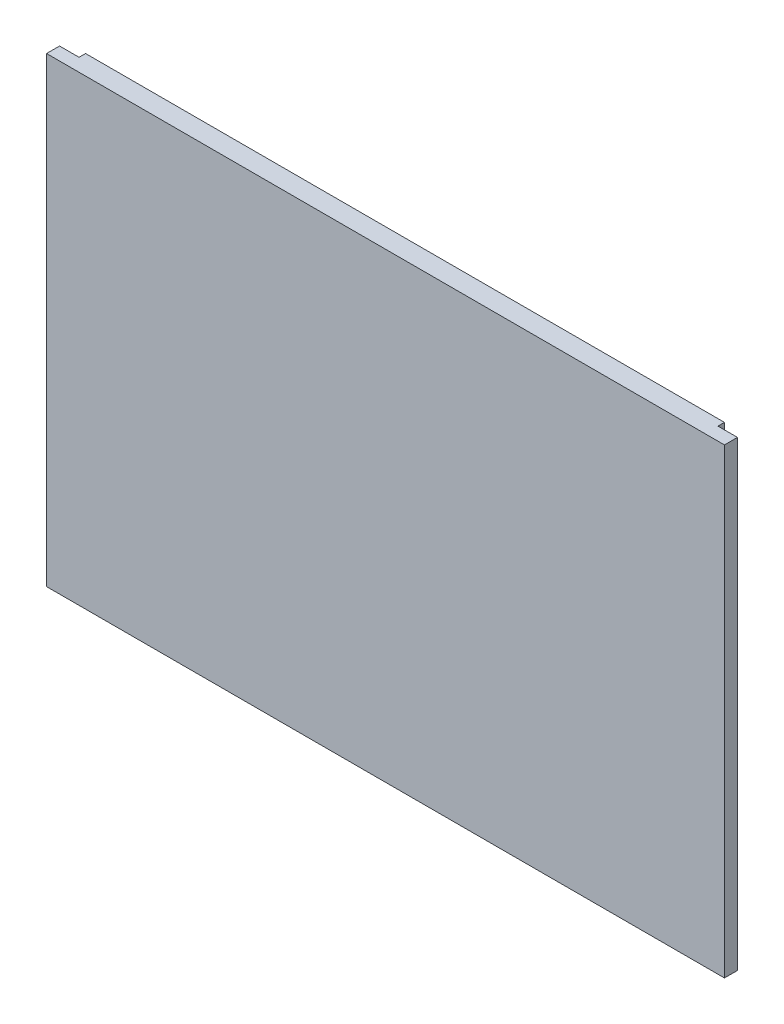
SolidWorks part; units mm, degrees
material "Pine"
ref_plane "Front Plane" through (0, 0, 0) normal (0, 0, 1) x (1, 0, 0)
ref_plane "Top Plane" through (0, 0, 0) normal (0, 1, 0) x (1, 0, 0)
ref_plane "Right Plane" through (0, 0, 0) normal (1, 0, 0) x (0, 0, -1)
sketch "Sketch5" plane through (0, 0, 0) normal (0, 0, 1) x (1, 0, 0)
  line L6 (0, 0) -> (417, 0)
  line L7 (0, 0) -> (0, 284)
  line L8 (0, 284) -> (417, 284)
  line L9 (417, 0) -> (417, 284)
  dimension "D1" = 417
  dimension "D2" = 284
extrude "Panel Ply" add sketch "Sketch5" along normal blind 12 separate body
sketch "Sketch6" plane through (0, 0, 0) normal (0, 0, -1) x (-1, 0, 0)
  line L0 (0, 0) -> (-417, 0) construction
  line L1 (-417, 284) -> (-405, 284)
  line L2 (-417, 284) -> (-417, 0)
  line L3 (-417, 0) -> (-405, 0)
  line L4 (-405, 284) -> (-405, 0)
  line L6 (0, 284) -> (-12, 284)
  line L7 (0, 284) -> (0, 0)
  line L8 (0, 0) -> (-12, 0)
  line L9 (-12, 284) -> (-12, 0)
  dimension "D1" = 12
  dimension "D2" = 12
extrude "Vertical Housing Cut" cut sketch "Sketch6" against normal blind 4
sketch "Sketch7" plane through (0, 0, 0) normal (0, 0, -1) x (-1, 0, 0)
  line L0 (-405, 0) -> (-405, 284) construction
  line L1 (-405, 136) -> (-12, 136)
  line L2 (-405, 136) -> (-405, 148)
  line L3 (-405, 148) -> (-12, 148)
  line L4 (-12, 136) -> (-12, 148)
  line L5 (-12, 284) -> (-12, 0) construction
  line L6 (-405, 284) -> (-12, 284) construction
  dimension "D1" = 12
  dimension "D2" = 136
extrude "Horizontal Housing Cut" cut sketch "Sketch7" against normal blind 4
equation "\"LENGTH\" = 1000mm"
equation "\"PLY\"= 12mm"
equation "\"CENTER_BRACE_LENGTH\" = 393mm"
equation "\"PANEL_WIDTH\"= \"LENGTH\" - \"CENTER_BRACE_LENGTH\" * 2 - \"PLY\" * 4"
equation "\"D1@Panel Ply\" = \"PLY\""
equation "\"D1@Sketch5\"=\"LENGTH\"/2 - \"PANEL_WIDTH\"/2"
equation "\"WIDTH\" = 300mm"
equation "\"HEIGHT\" = 300mm"
equation "\"HOUSING_DEPTH\" = 4mm"
equation "\"PANEL_SMALL_HEIGHT\" = 70mm"
equation "\"PORT_WIDTH\" = 90mm"
equation "\"PORT_RADIUS\" = 15mm"
equation "\"PORT_BRACE_HEIGHT\" = 92mm"
equation "\"DOWEL_SIZE\" = 0.25in"
equation "\"DOWEL_OFFSET\" = 30mm"
equation "\"D2@Sketch5\"=\"WIDTH\" - \"PLY\" * 2 + \"HOUSING_DEPTH\" * 2"
equation "\"D1@Sketch6\"=\"PLY\""
equation "\"D2@Sketch6\"=\"PLY\""
equation "\"D1@Vertical Housing Cut\" = \"HOUSING_DEPTH\""
equation "\"D1@Sketch7\"=\"PLY\""
equation "\"D2@Sketch7\"=(\"WIDTH\" - \"PLY\" * 2 + \"HOUSING_DEPTH\" * 2) / 2 - \"PLY\" / 2"
equation "\"D1@Horizontal Housing Cut\"=\"HOUSING_DEPTH\""
